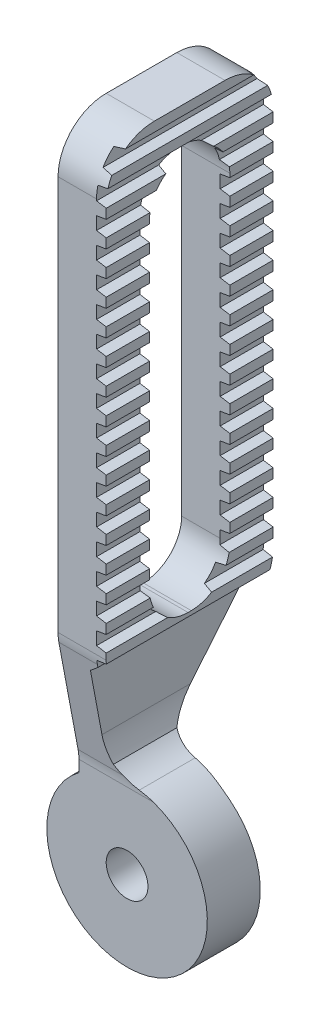
SolidWorks part; units mm, degrees
ref_plane "Front Plane" through (0, 0, 0) normal (0, 0, 1) x (1, 0, 0)
ref_plane "Top Plane" through (0, 0, 0) normal (0, 1, 0) x (1, 0, 0)
ref_plane "Right Plane" through (0, 0, 0) normal (1, 0, 0) x (0, 0, -1)
sketch "Sketch1" plane through (0, 0, 0) normal (0, 0, 1) x (1, 0, 0)
  circle A0 centre (0, 0) radius 2.5
  dimension "D1" = 5
extrude "Extrude1" add sketch "Sketch1" along normal blind 1.65
sketch "Sketch2" plane through (0, 0, 1.65) normal (0, 0, 1) x (1, 0, 0)
  circle A0 centre (0, 0) radius 0.65
  dimension "D1" = 1.3
extrude "Extrude2" cut sketch "Sketch2" against normal through all
sketch "Sketch3" plane through (0, 0, 0) normal (0, 1, 0) x (1, 0, 0)
  line L0 (-2.5, -1.65) -> (2.5, -1.65) construction
  line L1 (-1.5, 2.9) -> (0, 2.9)
  line L2 (-1.5, 2.9) -> (-1.5, -2.3)
  line L3 (-1.5, -2.3) -> (0, -2.3)
  line L4 (0, 2.9) -> (0, -2.3)
  line L6 (0.65, -1.65) -> (0.65, 0) construction
  dimension "D1" = 0.65
  dimension "D2" = 5.2
  dimension "D3" = 1.5
  dimension "D4" = 0.65
extrude "Extrude4" add sketch "Sketch3" along normal blind 19.9
sketch "Sketch4" plane through (0, 0, 0) normal (1, 0, 0) x (0, 0, -1)
  line L0 (0, 0) -> (0, 2.5)
  line L3 (0, -2.5) -> (0, 2.5) construction
  line L4 (0, 2.5) -> (2.9, 6)
  line L5 (2.9, 19.9) -> (2.9, 0) construction
  line L6 (2.9, 6) -> (2.9, 1.4932)
  line L7 (2.9, 1.4932) -> (2.9, 0)
  line L8 (-2.3, 0) -> (2.9, 0) construction
  line L9 (2.9, 0) -> (0, 0)
  dimension "D1" = 4.5068
  dimension "D2" = 3.5
extrude "Extrude5" cut sketch "Sketch4" against normal through all
fillet "Fillet1" radius 1.5 2 edges at (-0.75, 19.9, 2.3) (-0.75, 19.9, -2.9)
sketch "Sketch5" plane through (0, 0, 0) normal (1, 0, 0) x (0, 0, -1)
  line L0 (-2.3, 18.4) -> (-2.3, 0) construction
  line L1 (0.25, 18.52) -> (0.35, 18.52)
  line L2 (-0.95, 17.32) -> (-0.95, 7.32)
  line L3 (0.25, 6.12) -> (0.35, 6.12)
  line L4 (1.55, 17.32) -> (1.55, 7.32)
  line L7 (-0.8, 19.9) -> (1.4, 19.9) construction
  arc A0 (0.35, 18.52) -> (1.55, 17.32) centre (0.35, 17.32) cw
  arc A1 (0.25, 18.52) -> (-0.95, 17.32) centre (0.25, 17.32) ccw
  arc A2 (0.25, 6.12) -> (-0.95, 7.32) centre (0.25, 7.32) cw
  arc A3 (1.55, 7.32) -> (0.35, 6.12) centre (0.35, 7.32) cw
  point P10 (1.55, 18.52)
  point P13 (-0.95, 18.52)
  point P16 (-0.95, 6.12)
  dimension "D5" = 1.2
  dimension "D6" = 1.2
  dimension "D1" = 12.4
  dimension "D2" = 2.5
  dimension "D3" = 1.35
  dimension "D4" = 1.38
extrude "Extrude6" cut sketch "Sketch5" against normal through all
sketch "Sketch6" plane through (0, 0, 0) normal (1, 0, 0) x (0, 0, -1)
  line L0 (-1.65, 0) -> (-3.658, 0)
  line L1 (-3.658, 0) -> (-3.658, 5.9662)
  line L3 (-3.658, 5.9662) -> (-2.3, 5.9662)
  line L4 (-2.3, 18.4) -> (-2.3, 0) construction
  line L5 (-2.3, 5.9662) -> (-1.65, 2.5)
  line L6 (-1.65, 2.5) -> (-1.65, 0)
extrude "Extrude7" cut sketch "Sketch6" against normal through all
sketch "Sketch7" plane through (0, 0, 0) normal (0, 0, -1) x (-1, 0, 0)
  circle A0 centre (0, 0) radius 0.65
extrude "Extrude8" cut sketch "Sketch7" against normal through all
sketch "Sketch9" plane through (0, 0, 2.3) normal (0, 0, 1) x (1, 0, 0)
  line L0 (0, 19.6) -> (-0.3, 19.55)
  line L1 (0, 18.3) -> (0, 18.8)
  line L2 (0, 18.4) -> (0, 19.9) construction
  line L3 (-0.3, 19.55) -> (-0.3, 19.15)
  line L4 (-0.3, 19.15) -> (0, 19.1)
  line L5 (0, 19.1) -> (0, 19.6)
  line L6 (0, 18.8) -> (-0.3, 18.75)
  line L7 (-0.3, 18.75) -> (-0.3, 18.35)
  line L8 (-0.3, 18.35) -> (0, 18.3)
  line L9 (0, 17.5) -> (0, 18)
  line L10 (0, 18) -> (-0.3, 17.95)
  line L11 (-0.3, 17.95) -> (-0.3, 17.55)
  line L12 (-0.3, 17.55) -> (0, 17.5)
  line L13 (0, 16.7) -> (0, 17.2)
  line L14 (0, 17.2) -> (-0.3, 17.15)
  line L15 (-0.3, 17.15) -> (-0.3, 16.75)
  line L16 (-0.3, 16.75) -> (0, 16.7)
  line L17 (0, 15.9) -> (0, 16.4)
  line L18 (0, 16.4) -> (-0.3, 16.35)
  line L19 (-0.3, 16.35) -> (-0.3, 15.95)
  line L20 (-0.3, 15.95) -> (0, 15.9)
  line L21 (0, 15.1) -> (0, 15.6)
  line L22 (0, 15.6) -> (-0.3, 15.55)
  line L23 (-0.3, 15.55) -> (-0.3, 15.15)
  line L24 (-0.3, 15.15) -> (0, 15.1)
  line L25 (0, 14.3) -> (0, 14.8)
  line L26 (0, 14.8) -> (-0.3, 14.75)
  line L27 (-0.3, 14.75) -> (-0.3, 14.35)
  line L28 (-0.3, 14.35) -> (0, 14.3)
  line L29 (0, 13.5) -> (0, 14)
  line L30 (0, 14) -> (-0.3, 13.95)
  line L31 (-0.3, 13.95) -> (-0.3, 13.55)
  line L32 (-0.3, 13.55) -> (0, 13.5)
  line L33 (0, 12.7) -> (0, 13.2)
  line L34 (0, 13.2) -> (-0.3, 13.15)
  line L35 (-0.3, 13.15) -> (-0.3, 12.75)
  line L36 (-0.3, 12.75) -> (0, 12.7)
  line L37 (0, 11.9) -> (0, 12.4)
  line L38 (0, 12.4) -> (-0.3, 12.35)
  line L39 (-0.3, 12.35) -> (-0.3, 11.95)
  line L40 (-0.3, 11.95) -> (0, 11.9)
  line L41 (0, 11.1) -> (0, 11.6)
  line L42 (0, 11.6) -> (-0.3, 11.55)
  line L43 (-0.3, 11.55) -> (-0.3, 11.15)
  line L44 (-0.3, 11.15) -> (0, 11.1)
  line L45 (0, 10.3) -> (0, 10.8)
  line L46 (0, 10.8) -> (-0.3, 10.75)
  line L47 (-0.3, 10.75) -> (-0.3, 10.35)
  line L48 (-0.3, 10.35) -> (0, 10.3)
  line L49 (0, 9.5) -> (0, 10)
  line L50 (0, 10) -> (-0.3, 9.95)
  line L51 (-0.3, 9.95) -> (-0.3, 9.55)
  line L52 (-0.3, 9.55) -> (0, 9.5)
  line L53 (0, 8.7) -> (0, 9.2)
  line L54 (0, 9.2) -> (-0.3, 9.15)
  line L55 (-0.3, 9.15) -> (-0.3, 8.75)
  line L56 (-0.3, 8.75) -> (0, 8.7)
  line L57 (0, 7.9) -> (0, 8.4)
  line L58 (0, 8.4) -> (-0.3, 8.35)
  line L59 (-0.3, 8.35) -> (-0.3, 7.95)
  line L60 (-0.3, 7.95) -> (0, 7.9)
  line L61 (0, 7.1) -> (0, 7.6)
  line L62 (0, 7.6) -> (-0.3, 7.55)
  line L63 (-0.3, 7.55) -> (-0.3, 7.15)
  line L64 (-0.3, 7.15) -> (0, 7.1)
  line L65 (0, 6.3) -> (0, 6.8)
  line L66 (0, 6.8) -> (-0.3, 6.75)
  line L67 (-0.3, 6.75) -> (-0.3, 6.35)
  line L68 (-0.3, 6.35) -> (0, 6.3)
  line L69 (0, 5.5) -> (0, 6)
  line L70 (0, 6) -> (-0.3, 5.95)
  line L71 (-0.3, 5.95) -> (-0.3, 5.55)
  line L72 (-0.3, 5.55) -> (0, 5.5)
  dimension "D1" = 0.5
  dimension "D2" = 0.3
  dimension "D3" = 0.05
  dimension "D4" = 0.05
  dimension "D5" = 0.3
extrude "Extrude10" cut sketch "Sketch9" against normal through all
sketch "Sketch11" plane through (0, 0, 2.3) normal (0, 0, 1) x (1, 0, 0)
  line L0 (0, 6) -> (-0.5786, 5.5)
  line L1 (0, 2.5) -> (0, 5.5) construction
  line L2 (-0.5786, 5.5) -> (-0.5786, 3)
  line L3 (-0.5786, 3) -> (0, 2.5)
  line L4 (0, 2.5) -> (0, 6)
  dimension "D1" = 0.5
  dimension "D2" = 0.5
extrude "Extrude11" cut sketch "Sketch11" against normal through all
fillet "Fillet2" radius 1.5 3 edges at (-0.75, 2.5, 0) (-0.75, 2.5, 1.65) (0, 2.5, 0.825)
fillet "Fillet3" radius 1.5 3 edges at (-0.5786, 3, 0.6647) (-0.75, 6, -2.9) (-0.8515, 5.9662, 2.3)
ref_point "Point1"
